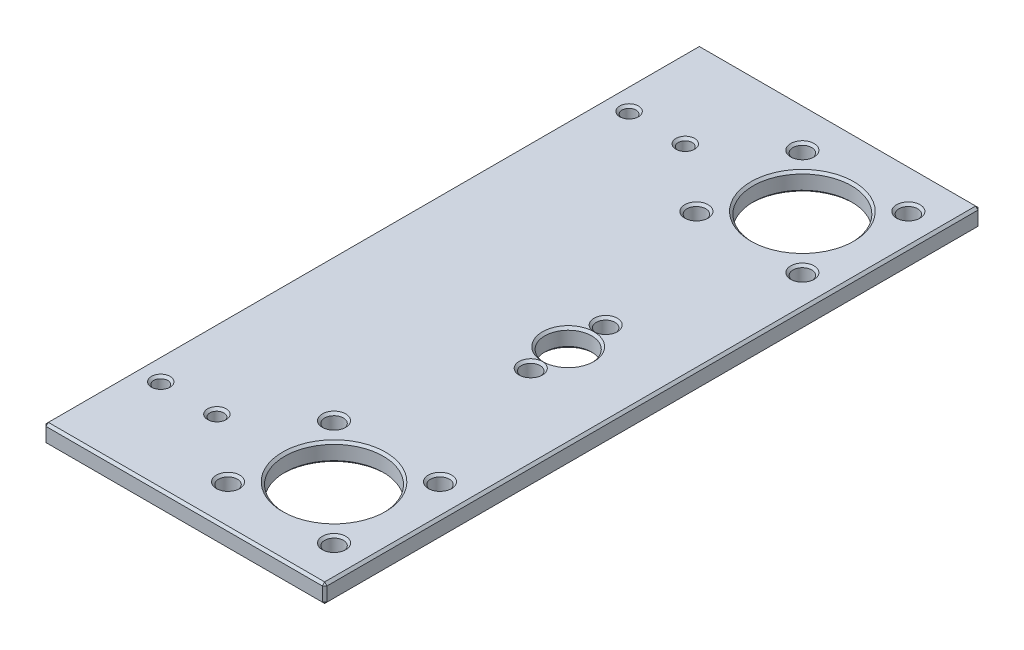
SolidWorks part; units mm, degrees
ref_plane "Alzado" through (0, 0, 0) normal (0, 0, 1) x (1, 0, 0)
ref_plane "Planta" through (0, 0, 0) normal (0, 1, 0) x (1, 0, 0)
ref_plane "Vista lateral" through (0, 0, 0) normal (1, 0, 0) x (0, 0, -1)
sketch "Croquis1" plane through (0, 0, 0) normal (0, 1, 0) x (1, 0, 0)
  line L0 (3.2717, -51.0414) -> (19.1899, -51.0414) construction
  line L1 (-38.7283, 68.9586) -> (21.2717, 68.9586)
  line L2 (-38.7283, 68.9586) -> (-38.7283, -71.0414)
  line L3 (-38.7283, -71.0414) -> (21.2717, -71.0414)
  line L4 (21.2717, 68.9586) -> (21.2717, -71.0414)
  line L5 (3.2717, -51.0414) -> (14.5854, -39.7277) construction
  line L6 (3.2717, -51.0414) -> (3.2717, -55.3682) construction
  line L7 (4.087, -1.0414) -> (20.0515, -1.0414) construction
  circle A0 centre (3.2717, 6.9586) radius 2
  circle A1 centre (3.2717, -9.0414) radius 2
  circle A2 centre (14.5854, 60.2723) radius 2
  circle A3 centre (14.5854, -39.7277) radius 2
  circle A4 centre (-8.042, -39.7277) radius 2
  circle A5 centre (-8.042, -62.3551) radius 2
  circle A6 centre (3.2717, -1.0414) radius 5
  circle A7 centre (14.5854, -62.3551) radius 2
  circle A8 centre (3.2717, -51.0414) radius 10.5
  circle A9 centre (3.2717, 48.9586) radius 10.5
  circle A10 centre (-8.042, 60.2723) radius 2
  circle A11 centre (14.5854, 37.6449) radius 2
  circle A12 centre (-8.042, 37.6449) radius 2
  circle A13 centre (-21.7283, -51.0414) radius 1.5
  circle A14 centre (-33.7283, -51.0414) radius 1.5
  circle A15 centre (-21.7283, 48.9586) radius 1.5
  circle A16 centre (-33.7283, 48.9586) radius 1.5
  dimension "D7" = 18
  dimension "D8" = 45
  dimension "D9" = 4
  dimension "D10" = 3
  dimension "D11" = 3
  dimension "D12" = 25
  dimension "D17" = 60
  dimension "D16" = 10
  dimension "D20" = 21
  dimension "D21" = 21
  dimension "D4" = 4
  dimension "D5" = 8
  dimension "D3" = 4
  dimension "D6" = 8
  dimension "D13" = 12
  dimension "D14" = 140
  dimension "D15" = 20
  dimension "D22" = 50
  dimension "D23" = 50
extrude "Saliente-Extruir1" add sketch "Croquis1" along normal blind 4
chamfer "Chaflán1" distance 0.5 angle 45 46 edges at (-38.7283, 2, -68.9586) (-38.7283, 2, 71.0414) (21.2717, 2, 71.0414) (-8.7283, 0, 71.0414) (21.2717, 0, 1.0414) (-38.7283, 0, 1.0414) (-8.7283, 0, -68.9586) (21.2717, 2, -68.9586) (-8.7283, 4, -68.9586) (21.2717, 4, 1.0414) (-8.7283, 4, 71.0414) (-38.7283, 4, 1.0414) (3.2717, 0, 6.0414) (3.2717, 4, 6.0414) (3.2717, 0, -38.4586) (3.2717, 0, 61.5414) (3.2717, 4, -38.4586) (3.2717, 4, 61.5414) (-33.7283, 0, -50.4586) (-33.7283, 0, 52.5414) (-8.042, 0, -35.6449) (-8.042, 0, -62.2723) (14.5854, 0, 60.3551) (14.5854, 0, 41.7277) (3.2717, 0, -4.9586) (3.2717, 0, 11.0414) (-8.042, 0, 37.7277) (-8.042, 0, 64.3551) (14.5854, 0, -58.2723) (14.5854, 0, -39.6449) (-21.7283, 0, 52.5414) (-21.7283, 0, -50.4586) (-33.7283, 4, -50.4586) (-33.7283, 4, 52.5414) (-8.042, 4, -35.6449) (-8.042, 4, -62.2723) (14.5854, 4, 60.3551) (14.5854, 4, 41.7277) (3.2717, 4, -4.9586) (3.2717, 4, 11.0414) (-8.042, 4, 37.7277) (-8.042, 4, 64.3551) (14.5854, 4, -58.2723) (14.5854, 4, -39.6449) (-21.7283, 4, 52.5414) (-21.7283, 4, -50.4586)
